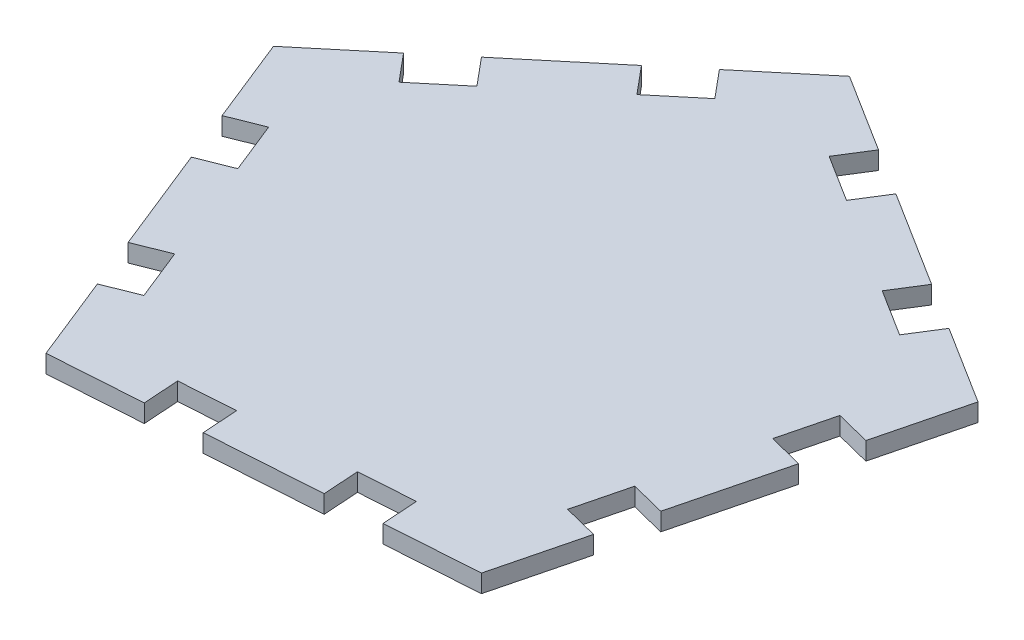
SolidWorks part; units mm, degrees
ref_plane "Front Plane" through (0, 0, 0) normal (0, 0, 1) x (1, 0, 0)
ref_plane "Top Plane" through (0, 0, 0) normal (0, 1, 0) x (1, 0, 0)
ref_plane "Right Plane" through (0, 0, 0) normal (1, 0, 0) x (0, 0, -1)
sketch "Sketch1" plane through (0, 0, 0) normal (0, 1, 0) x (1, 0, 0)
  line L1 (-59.9258, 15.1181) -> (-32.8962, -52.3211)
  line L2 (-32.8962, -52.3211) -> (39.5948, -47.4543)
  line L3 (39.5948, -47.4543) -> (57.3672, 22.9927)
  line L4 (57.3672, 22.9927) -> (-4.14, 61.6646)
  line L5 (-4.14, 61.6646) -> (-59.9258, 15.1181)
  circle A0 centre (0, 0) radius 50 construction
  dimension "D1" = 100
extrude "Boss-Extrude1" add sketch "Sketch1" along normal blind 3.18
ref_axis "Axis" through (0, 3.339, 0) along (0, -1, 0)
sketch "Axis Check" [suppressed] plane through (0, 3.18, 0) normal (0, 1, 0) x (1, 0, 0)
  line L0 (3.3493, -49.8877) -> (-4.14, 61.6646) construction
  line L1 (-32.8962, -52.3211) -> (39.5948, -47.4543) construction
  line L2 (57.3672, 22.9927) -> (-46.411, -18.6015) construction
  line L3 (-59.9258, 15.1181) -> (-32.8962, -52.3211) construction
  line L4 (-32.0329, 38.3913) -> (39.5948, -47.4543) construction
  line L5 (-4.14, 61.6646) -> (-59.9258, 15.1181) construction
  line L6 (-59.9258, 15.1181) -> (48.481, -12.2308) construction
  line L7 (39.5948, -47.4543) -> (57.3672, 22.9927) construction
  line L8 (-32.8962, -52.3211) -> (26.6136, 42.3287) construction
  line L9 (57.3672, 22.9927) -> (-4.14, 61.6646) construction
sketch "Sketch2" plane through (0, 0, 0) normal (0, -1, 0) x (1, 0, 0)
  line L0 (-53.8219, 0.1114) -> (-47.9184, -2.2547)
  line L1 (-53.8219, 0.1114) -> (-50.1648, 9.2358)
  line L2 (-47.9184, -2.2547) -> (-44.2613, 6.8697)
  line L3 (-50.1648, 9.2358) -> (-44.2613, 6.8697)
  line L4 (-59.9258, -15.1181) -> (-32.8962, 52.3211) construction
  line L5 (-42.6572, 27.9673) -> (-39.0002, 37.0917)
  line L6 (-42.6572, 27.9673) -> (-36.7538, 25.6012)
  line L7 (-39.0002, 37.0917) -> (-33.0967, 34.7256)
  line L8 (-36.7538, 25.6012) -> (-33.0967, 34.7256)
  line L9 (-46.411, 18.6015) -> (-19.2439, 7.7129) construction
  line L10 (-40.8287, 32.5295) -> (-34.9252, 30.1634) construction
  dimension "D1" = 6.36
  dimension "D3" = 10.09
  dimension "D2" = 9.83
extrude "Cut F" cut sketch "Sketch2" against normal through all
sketch "Sketch4" [suppressed] plane through (0, 3.18, 0) normal (0, 1, 0) x (1, 0, 0)
  line L9 (26.6136, 42.3287) -> (-26.6136, -42.3287) construction
  line L10 (57.3672, 22.9927) -> (-4.14, 61.6646) construction
  line L11 (-34.4964, -17.2915) -> (0.6335, 38.5824)
  line L12 (-34.4964, -17.2915) -> (-0.6335, -38.5824)
  line L13 (0.6335, 38.5824) -> (34.4964, 17.2915)
  line L14 (-0.6335, -38.5824) -> (34.4964, 17.2915)
  line L15 (-34.4964, -17.2915) -> (34.4964, 17.2915) construction
  line L16 (0.6335, 38.5824) -> (-0.6335, -38.5824) construction
  line L20 (0, 0) -> (39.0006, -24.5211) construction
  circle A0 centre (-21.8232, -34.7095) radius 3.25
  circle A1 centre (23.7041, -14.9036) radius 3.25
  point P5 (0, 0)
  point P6 (-21.8232, -34.7095)
  dimension "D3" = 6.5
  dimension "D1" = 40
  dimension "D2" = 66
  dimension "D4" = 8
  dimension "D5" = 8
extrude "Top Cut" [suppressed] cut sketch "Sketch4" against normal blind 10
sketch "Sketch7" [suppressed] plane through (0, 3.18, 0) normal (0, 1, 0) x (1, 0, 0)
  line L0 (0, 0) -> (26.6136, 42.3287) construction
  line L1 (57.3672, 22.9927) -> (-4.14, 61.6646) construction
  line L2 (-7.1857, -11.4287) -> (-30.8897, 3.4749) construction
  line L3 (-14.3588, -11.6437) -> (-33.0188, 0.0886) construction
  line L5 (0.6335, 38.5824) -> (-34.4964, -17.2915) construction
  circle A0 centre (-30.8897, 3.4749) radius 1
  circle A1 centre (-33.0188, 0.0886) radius 1
  dimension "D5" = 2
  dimension "D1" = 4
  dimension "D2" = 17.5
  dimension "D3" = 8
  dimension "D4" = 8
extrude "Top Cut 2" [suppressed] cut sketch "Sketch7" against normal through all
sketch "Sketch10" [suppressed] plane through (0, 3.18, 0) normal (0, 1, 0) x (1, 0, 0)
  line L0 (26.6136, 42.3287) -> (17.565, 27.9369) construction
  line L1 (57.3672, 22.9927) -> (-4.14, 61.6646) construction
  line L2 (34.4964, 17.2915) -> (0.6335, 38.5824) construction
  line L3 (33.0578, 31.7802) -> (13.6147, 44.0048) construction
  line L4 (34.4964, 17.2915) -> (0.6335, 38.5824) construction
  circle A0 centre (19.4532, 40.3339) radius 1
  circle A1 centre (27.919, 35.0111) radius 1
  dimension "D1" = 11.5
  dimension "D2" = 2
  dimension "D3" = 5
extrude "Top Cut 3" [suppressed] cut sketch "Sketch10" against normal blind 10
sketch "Sketch8" [suppressed] plane through (0, 3.18, 0) normal (0, 1, 0) x (1, 0, 0)
  line L0 (3.3493, -49.8877) -> (-4.14, 61.6646) construction
  line L5 (-32.8962, -52.3211) -> (39.5948, -47.4543) construction
  line L6 (-17.9455, -31.2723) -> (21.9647, -28.5929)
  line L11 (-17.9455, -31.2723) -> (-21.9647, 28.5929)
  line L12 (21.9647, -28.5929) -> (17.9455, 31.2723)
  line L13 (-21.9647, 28.5929) -> (17.9455, 31.2723)
  point P4 (1.4955, -22.2759)
  dimension "D1" = 60
  dimension "D2" = 40
  dimension "D3" = 20
extrude "Bottom Cut" [suppressed] cut sketch "Sketch8" against normal blind 10
sketch "Sketch9" [suppressed] plane through (0, 3.18, 0) normal (0, 1, 0) x (1, 0, 0)
  line L0 (19.9551, 1.3397) -> (-19.9551, -1.3397) construction
  line L1 (21.9647, -28.5929) -> (17.9455, 31.2723) construction
  line L2 (-21.9647, 28.5929) -> (-17.9455, -31.2723) construction
  line L3 (-19.9551, -1.3397) -> (-44.4689, -2.9855) construction
  line L4 (19.9551, 1.3397) -> (42.6839, 2.8657) construction
  line L5 (-32.8962, -52.3211) -> (39.5948, -47.4543) construction
  line L6 (-29.6051, -6.8886) -> (-32.3788, -7.0748)
  line L7 (-29.6051, -6.8886) -> (-30.2602, 2.8694)
  line L8 (-30.2602, 2.8694) -> (-33.0339, 2.6832)
  line L9 (-32.3788, -7.0748) -> (-33.0339, 2.6832)
  line L10 (-29.6051, -6.8886) -> (-33.0339, 2.6832) construction
  line L11 (-30.2602, 2.8694) -> (-32.3788, -7.0748) construction
  line L12 (33.0339, -2.6832) -> (30.2602, -2.8694)
  line L13 (33.0339, -2.6832) -> (32.3788, 7.0748)
  line L14 (32.3788, 7.0748) -> (29.6051, 6.8886)
  line L15 (30.2602, -2.8694) -> (29.6051, 6.8886)
  line L16 (33.0339, -2.6832) -> (29.6051, 6.8886) construction
  line L17 (32.3788, 7.0748) -> (30.2602, -2.8694) construction
  line L18 (-32.8962, -52.3211) -> (39.5948, -47.4543) construction
  point P6 (-31.3195, -2.1027)
  point P13 (31.3195, 2.1027)
  dimension "D1" = 9.83
  dimension "D4" = 9.83
  dimension "D5" = 10
  dimension "D6" = 10
  dimension "D2" = 2.78
  dimension "D3" = 2.78
extrude "Battery Holder Cut" [suppressed] cut sketch "Sketch9" against normal blind 6.36
sketch "Sketch3" [suppressed] plane through (0, 3.18, 0) normal (0, 1, 0) x (1, 0, 0)
  line L0 (0, 0) -> (-40.9819, 49.1167) construction
  line L1 (-51.5331, 30.4039) -> (-43.3839, 20.6371)
  line L3 (-43.3839, 20.6371) -> (-35.5751, 27.1526)
  line L4 (-43.7243, 36.9194) -> (-35.5751, 27.1526)
  line L5 (-4.14, 61.6646) -> (-59.9258, 15.1181) construction
  line L6 (-71.9961, 5.0469) -> (-69.9588, 2.6052)
  line L7 (-71.9961, 5.0469) -> (-47.4739, 25.5077)
  line L14 (-28.4906, 49.63) -> (-20.3415, 39.8633)
  line L16 (-20.3415, 39.8633) -> (-12.5327, 46.3788)
  line L17 (-20.6818, 56.1455) -> (-12.5327, 46.3788)
  line L18 (-40.5056, 25.1246) -> (-39.4795, 23.8949) construction
  line L19 (-51.5331, 30.4039) -> (-43.7243, 36.9194)
  line L21 (-28.4906, 49.63) -> (-20.6818, 56.1455)
  line L22 (-16.6073, 51.2621) -> (4.7866, 69.1127)
  line L23 (-39.6497, 32.036) -> (-24.4161, 44.7466)
  line M18 (-4.14, 61.6646) -> (-59.9258, 15.1181)
  dimension "D1" = 12.72
  dimension "D2" = 10.17
  dimension "D3" = 9.92
  dimension "D4" = 100
extrude "Extrude M" [suppressed] add sketch "Sketch3" against normal up to surface (3.18 mm away) contours L21 L14 L7 L17 | L19 L1 L4 M18 up to face at (-26.7442, 0, 10.7191)
pattern_circular "Circle F" count 5 over 360 about axis through (0, 3.339, 0) along (0, -1, 0) of "Cut F"
pattern_circular "Circle M" [suppressed] count 5 over 360 about axis through (0, 3.339, 0) along (0, -1, 0) of bodies 173
pattern_circular "Circle Side F" [suppressed] count 5 over 360 about axis through (0, 3.339, 0) along (0, -1, 0) of bodies 173
pattern_circular "Circle Side M" [suppressed] count 5 over 360 about axis through (0, 3.339, 0) along (0, -1, 0) of bodies 168
equation "\"kerf\" = .17mm"
equation "\"tabWidthF\"= 10 - \"kerf\""
equation "\"tabThickness\" = 6.36mm"
equation "\"D1@Sketch2\"=\"tabThickness\""
equation "\"tabWidthM\"= 10 + \"kerf\""
equation "\"halfkerf\"= \"kerf\" / 2.00mm"
equation "\"D1@Sketch9\"=\"tabWidthF\""
equation "\"D4@Sketch9\"=\"tabWidthF\""
equation "\"D1@Battery Holder Cut\" = \"tabThickness\""
equation "\"tabLength\" = \"kerf\" + 12"
